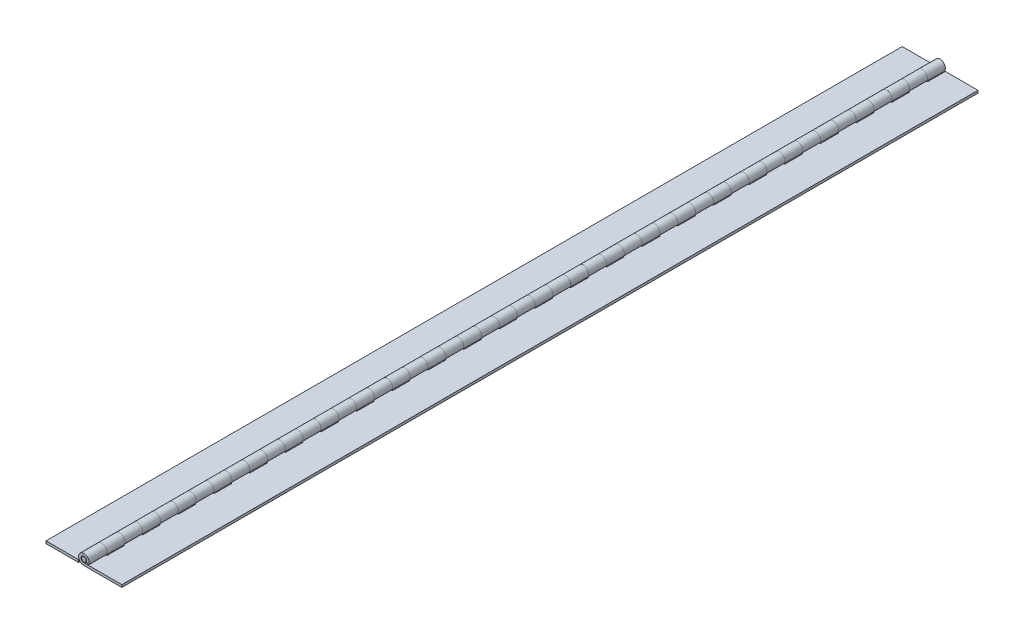
SolidWorks part; units mm, degrees
note: '?' marks a value the reader was unsure of.
ref_plane "Front Plane" through (0, 0, 0) normal (0, 0, 1) x (1, 0, 0)
ref_plane "Top Plane" through (0, 0, 0) normal (0, 1, 0) x (1, 0, 0)
ref_plane "Right Plane" through (0, 0, 0) normal (1, 0, 0) x (0, 0, -1)
sketch "Sketch1" plane through (0, 0, 0) normal (0, 0, 1) x (1, 0, 0)
  line L0 (1.5981, -0.9919) -> (13.4937, -0.9919)
  line L1 (13.4937, -0.9919) -> (13.4937, -1.8809)
  line L2 (13.4937, -1.8809) -> (0, -1.8809)
  line L3 (0, 0) -> (0, 0.9922) construction
  line L4 (-0.9922, 0) -> (-1.8809, 0) construction
  line L5 (0.8992, -0.4193) -> (1.7046, -0.7949) construction
  line L6 (-0.8992, -0.4193) -> (-1.7046, -0.7949) construction
  circle A0 centre (0, 0) radius 0.9922
  circle A1 centre (0, 0) radius 1.8809
  dimension "pin diameter" = 1.9844
  dimension "knuckle dia" = 3.7617
  dimension "leaf thickness" = 0.889
  dimension "open width" = 26.9875
  dimension "D5" = 25
  dimension "D6" = 25
sketch "Sketch2" plane through (0, 0, 0) normal (0, 0, 1) x (1, 0, 0)
  line L0 (13.4937, -0.9919) -> (13.4937, -1.8809) construction
  line L1 (1.5981, -0.9919) -> (13.4937, -0.9919) construction
  line L2 (0.8992, -0.4193) -> (1.7046, -0.7949) construction
  line L3 (13.4937, -1.8809) -> (0, -1.8809) construction
  line L4 (13.4937, -0.9919) -> (13.4937, -1.8809)
  line L5 (-0.0251, -0.9919) -> (13.4937, -0.9919)
  line L6 (0.8992, -0.4193) -> (1.7046, -0.7949)
  line L7 (13.4937, -1.8809) -> (0, -1.8809)
  circle A0 centre (0, 0) radius 0.9922 construction
  circle A1 centre (0, 0) radius 1.8809 construction
  arc A2 (0.8992, -0.4193) -> (-0.0251, -0.9919) centre (0, 0) ccw
  arc A3 (1.7046, -0.7949) -> (0, -1.8809) centre (0, 0) ccw
extrude "Extrude1" add sketch "Sketch2" along normal mid plane 304.8
sketch "Sketch3" plane through (0, -0.9919, 0) normal (0, 1, 0) x (1, 0, 0)
  line L1 (-1.8809, 152.4) -> (1.8809, 152.4)
  line L2 (-1.8809, 152.4) -> (-1.8809, 146.05)
  line L3 (-1.8809, 146.05) -> (1.8809, 146.05)
  line L4 (1.8809, 152.4) -> (1.8809, 146.05)
  line L6 (1.8809, 152.4) -> (-1.8809, 152.4) construction
  line L7 (1.8809, -152.4) -> (1.8809, 152.4) construction
  line L8 (-1.8809, 152.4) -> (-1.8809, -152.4) construction
  dimension "knuckle length" = 6.35
extrude "Cut-Extrude1" cut sketch "Sketch3" against normal mid plane 50.8
pattern_linear "LPattern1" count 24 spacing 12.7 along (0, 0, 1) of "Cut-Extrude1"
sketch "Sketch5" plane through (0, 0, -152.4) normal (0, 0, -1) x (-1, 0, 0)
  line L0 (-1.5981, -0.9919) -> (-13.4937, -0.9919) construction
  line L1 (-13.4937, -1.8809) -> (0, -1.8809) construction
  line L2 (0.0251, -0.9919) -> (13.4937, -0.9919)
  line L3 (13.4937, -1.8809) -> (0, -1.8809)
  line L4 (0.8992, -0.4193) -> (1.7046, -0.7949) construction
  line L5 (0.8992, -0.4193) -> (1.7046, -0.7949)
  line L6 (13.4937, -0.9919) -> (13.4937, -1.8809)
  line L8 (0, 0) -> (0, -1.8809) construction
  circle A0 centre (0, 0) radius 1.8809 construction
  arc A1 (1.7046, -0.7949) -> (0, -1.8809) centre (0, 0) ccw
  circle A2 centre (0, 0) radius 0.9922 construction
  arc A3 (0.8992, -0.4193) -> (0.0251, -0.9919) centre (0, 0) ccw
  dimension "D1" = 26.9875
extrude "Extrude2" add sketch "Sketch5" against normal blind 6.35 separate body
pattern_linear "LPattern3" count 24 spacing 12.7 along (0, 0, 1) of bodies 104
sketch "Sketch6" plane through (0, 0, -152.4) normal (0, 0, -1) x (-1, 0, 0)
  line L0 (0, -1.8809) -> (13.4937, -1.8809) construction
  line L1 (13.4937, -0.9919) -> (1.9063, -0.9919)
  line L2 (13.4937, -0.9919) -> (13.4937, -1.8809)
  line L3 (13.4937, -1.8809) -> (1.9063, -1.8809)
  line L4 (1.9063, -0.9919) -> (1.9063, -1.8809)
  line L6 (13.4937, -0.9919) -> (0.0251, -0.9919) construction
  line L7 (1.8809, 1.5054) -> (1.8809, -2.5761) construction
  arc A0 (1.7046, -0.7949) -> (0, -1.8809) centre (0, 0) ccw construction
  dimension "D1" = 0.0254
extrude "Extrude5" add sketch "Sketch6" against normal blind 304.8
sketch "Sketch7" plane through (0, 0, 0) normal (0, 0, 1) x (1, 0, 0)
  circle A0 centre (0, 0) radius 0.9922 construction
  circle A1 centre (0, 0) radius 0.9922
extrude "Extrude4" add sketch "Sketch7" along normal mid plane 304.8 separate body
chamfer "Chamfer1" distance 0.1984 angle 45 2 edges at (0.9922, 0, 152.4) (0.9922, 0, -152.4)
sketch "Sketch8" plane through (0, 0, 0) normal (0, 1, 0) x (1, 0, 0)
  line L0 (13.4938, 0) -> (-13.4937, 0) construction
  line L1 (13.4937, 0) -> (0, 0) construction
  line L2 (-13.4937, -152.4) -> (-13.4937, 152.4) construction
  line L3 (13.4937, -152.4) -> (13.4937, 152.4) construction
ref_axis "Axis1" through (-13.4937, 0, 0) along (1, 0, 0)?
ref_plane "  " through (0, 0, 0) normal (0, 0.866, 0.5) x (1, 0, 0)
sketch "Sketch9" plane through (0, 0, 0) normal (0, 1, 0) x (1, 0, 0)
  line L0 (1.8809, 146.05) -> (1.8809, 152.4) construction
  point P0 (-13.4937, 152.4)
  point P1 (13.4937, 152.4)
  point P3 (-13.4937, -152.4)
  point P5 (13.4937, -152.4)
  point P7 (1.8809, 146.05)
sketch "Sketch11" plane through (0, 0, 0) normal (0, 0, 1) x (1, 0, 0)
  line L0 (-1.8809, 0) -> (-1.8809, -1.8809)
  line L1 (-1.8809, -1.8809) -> (1.8809, -1.8809)
  line L2 (1.8809, -1.8809) -> (1.8809, 0)
  line L3 (0, -1.8809) -> (13.4937, -1.8809) construction
  circle A0 centre (0, 0) radius 1.8809
  circle A1 centre (0, 0) radius 1.8809 construction
equation "\"D1@LPattern1\" = \"overall length@Extrude1\"/(\"knuckle length@Sketch3\"*2)"
equation "\"D1@Sketch5\" = \"open width@Sketch1\""
equation "\"D1@LPattern3\" = \"D1@LPattern1\""
equation "\"D1@Extrude4\" = \"overall length@Extrude1\""
equation "\"D3@LPattern1\" = \"knuckle length@Sketch3\"*2"
equation "\"D3@LPattern3\" = \"D3@LPattern1\""
equation "\"D1@Chamfer1\" = \"pin diameter@Sketch1\"*.1"
equation "\"D1@Extrude2\" = \"knuckle length@Sketch3\""
equation "\"D1@Extrude5\" = \"overall length@Extrude1\""
